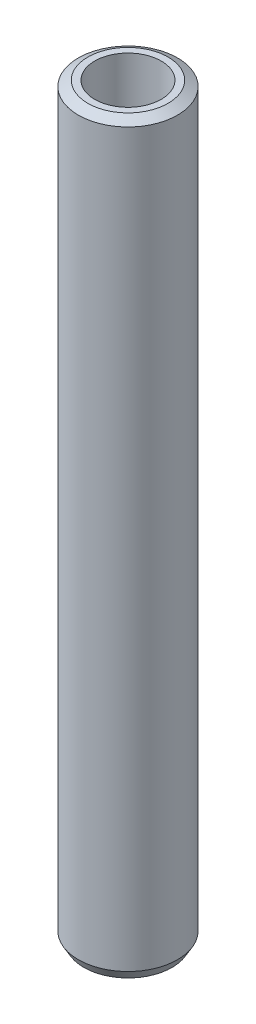
SolidWorks part; units mm, degrees
ref_plane "Front Plane" through (0, 0, 0) normal (0, 0, 1) x (1, 0, 0)
ref_plane "Top Plane" through (0, 0, 0) normal (0, 1, 0) x (1, 0, 0)
ref_plane "Right Plane" through (0, 0, 0) normal (1, 0, 0) x (0, 0, -1)
sketch "Sketch1" plane through (0, 0, 0) normal (0, 1, 0) x (1, 0, 0)
  circle A0 centre (0, 0) radius 27.5
  dimension "SHAFT_OD" = 55
extrude "Boss-Extrude1" add sketch "Sketch1" along normal blind 413.7056
sketch "Sketch2" plane through (0, 0, 0) normal (0, 1, 0) x (1, 0, 0)
  circle A0 centre (0, 0) radius 18.435
  dimension "BORE_D" = 36.87
extrude "Cut-Extrude1" cut sketch "Sketch2" along normal through all
chamfer "Chamfer1" distance 3.0362 angle 60 2 edges at (0, 413.7056, 27.5) (0, 0, 27.5) first distance on face at (0, 413.7056, 27.5) first distance on face at (0, 0, 18.435)
